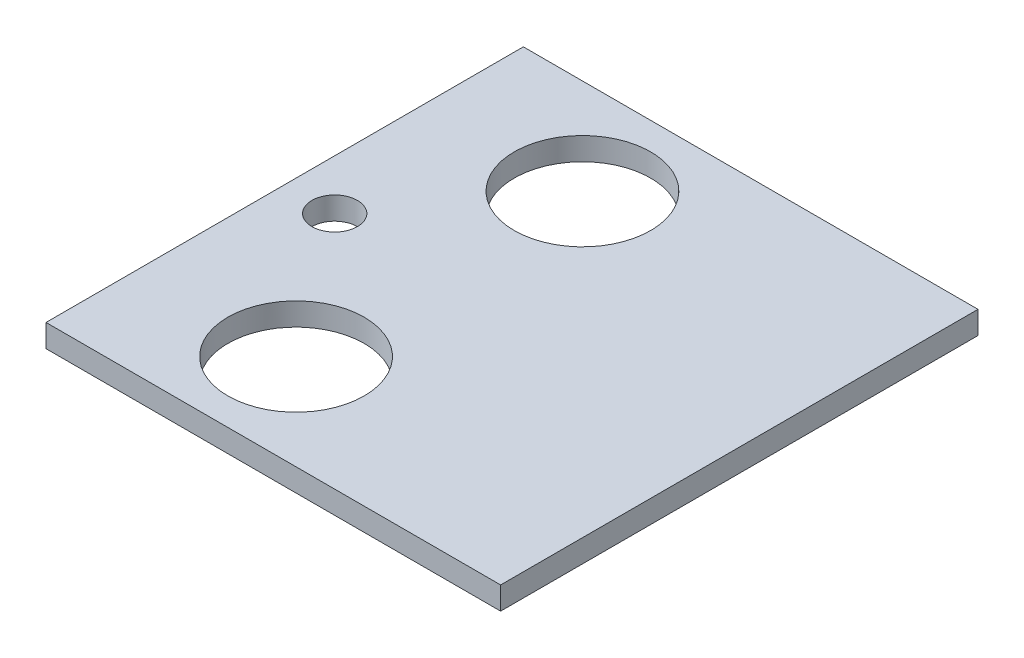
SolidWorks part; units mm, degrees
ref_plane "Front Plane" through (0, 0, 0) normal (0, 0, 1) x (1, 0, 0)
ref_plane "Top Plane" through (0, 0, 0) normal (0, 1, 0) x (1, 0, 0)
ref_plane "Right Plane" through (0, 0, 0) normal (1, 0, 0) x (0, 0, -1)
sketch "Sketch2" plane through (0, 0, 0) normal (0, 1, 0) x (1, 0, 0)
  line L0 (0, 80.9892) -> (0, -86.3988) construction
  line L1 (-50, 52.5) -> (50, 52.5)
  line L2 (-50, 52.5) -> (-50, -52.5)
  line L3 (-50, -52.5) -> (50, -52.5)
  line L4 (50, 52.5) -> (50, -52.5)
  line L5 (-89.0263, 0) -> (108.6553, 0) construction
  dimension "D1" = 100
  dimension "D2" = 105
extrude "Boss-Extrude1" add sketch "Sketch2" along normal blind 5
sketch "Sketch5" plane through (0, 0, 0) normal (0, -1, 0) x (1, 0, 0)
  line L0 (120.2435, 0) -> (-132.425, 0) construction
  line L1 (0, 87.6866) -> (0, -77.6809) construction
  line L4 (-50, 52.5) -> (50, 52.5) construction
  line L6 (-50, -52.5) -> (-50, 52.5) construction
  circle A0 centre (-39, 0) radius 39 construction
  circle A1 centre (-16.0054, 31.5) radius 15
  circle A2 centre (0, 0) radius 15 construction
  circle A4 centre (-39, 0) radius 5
  dimension "D1" = 30
  dimension "D2" = 6
  dimension "D3" = 30
  dimension "D4" = 10
  dimension "D6" = 78
  dimension "D5" = 6
extrude "Cut-Extrude1" cut sketch "Sketch5" against normal blind 6
mirror "Mirror1" about plane through (0, 0, 0) normal (0, 0, 1) of "Cut-Extrude1"
